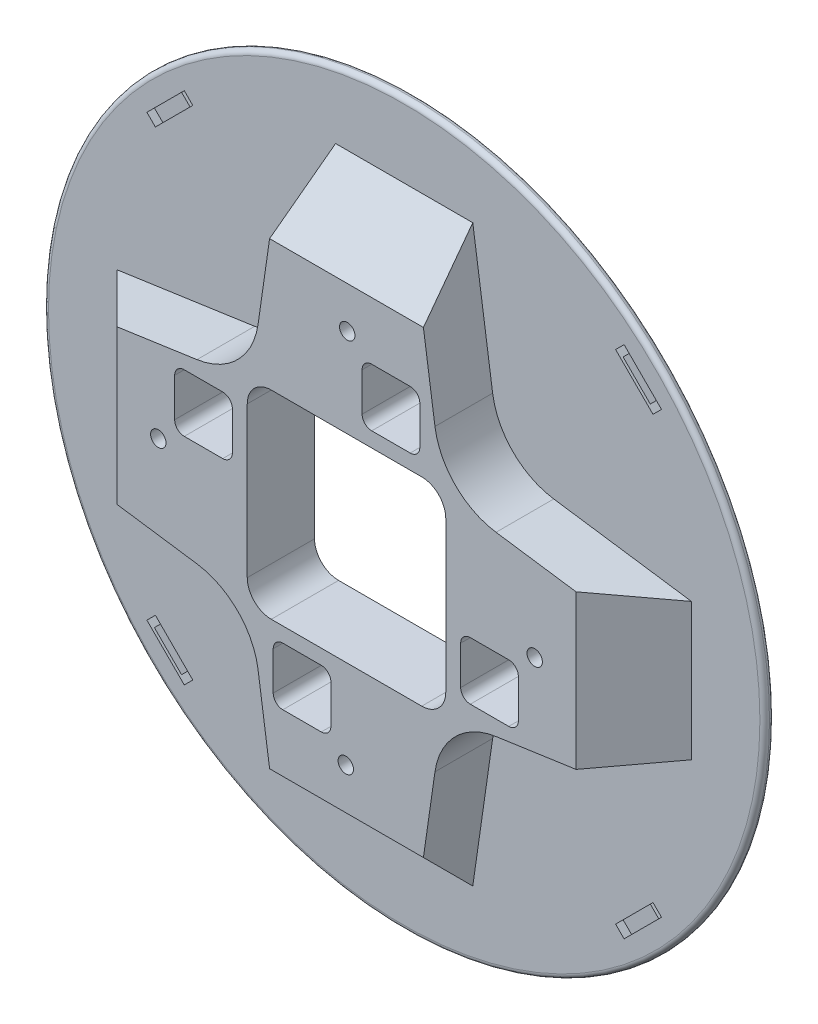
SolidWorks part; units mm, degrees
ref_plane "Front" through (0, 0, 0) normal (0, 0, 1) x (1, 0, 0)
ref_plane "Top" through (0, 0, 0) normal (0, 1, 0) x (1, 0, 0)
ref_plane "Right" through (0, 0, 0) normal (1, 0, 0) x (0, 0, -1)
sketch "ｽｹｯﾁ1" plane through (0, 0, 0) normal (0, 0, 1) x (1, 0, 0)
  line L1 (47.75, -47.75) -> (-47.75, -47.75)
  line L2 (47.75, -47.75) -> (47.75, 47.75)
  line L3 (47.75, 47.75) -> (-47.75, 47.75)
  line L4 (-47.75, -47.75) -> (-47.75, 47.75)
  line L5 (47.75, -47.75) -> (-47.75, 47.75) construction
  line L6 (47.75, 47.75) -> (-47.75, -47.75) construction
  point P0 (0, 0)
  dimension "D1" = 95.5
extrude "ﾎﾞｽ - 押し出し1" add sketch "ｽｹｯﾁ1" along normal blind 12
sketch "ｽｹｯﾁ2" plane through (0, 0, 12) normal (0, 0, 1) x (1, 0, 0)
  line L0 (-16, 47.75) -> (-20, 20)
  line L2 (-20, 20) -> (-47.75, 16)
  line L4 (-47.75, 16) -> (-47.75, 47.75)
  line L5 (-47.75, 47.75) -> (-16, 47.75)
  line L6 (-16, -47.75) -> (-20, -20)
  line L8 (-20, -20) -> (-47.75, -16)
  line L9 (-47.75, -16) -> (-47.75, -47.75)
  line L10 (-47.75, -47.75) -> (-16, -47.75)
  line L11 (0, 0) -> (-47.75, 47.75) construction
  line L12 (0, 0) -> (-47.75, -47.75) construction
  line L13 (-47.75, 47.75) -> (-47.75, -47.75) construction
  line L14 (-47.75, -47.75) -> (47.75, -47.75) construction
  dimension "D1" = 16
  dimension "D2" = 16
  dimension "D3" = 16
  dimension "D4" = 4
  dimension "D5" = 4
extrude "ｶｯﾄ - 押し出し1" cut sketch "ｽｹｯﾁ2" against normal through all
mirror "ﾐﾗｰ1" about plane through (0, 0, 0) normal (1, 0, 0) of "ｶｯﾄ - 押し出し1"
fillet "ﾌｨﾚｯﾄ2" radius 15 4 edges at (-20, 20, 6) (20, 20, 6) (20, -20, 6) (-20, -20, 6)
sketch "ｽｹｯﾁ3" plane through (0, 0, 0) normal (0, 0, -1) x (-1, 0, 0)
  circle A0 centre (0, 0) radius 75
  dimension "D1" = 150
extrude "ﾎﾞｽ - 押し出し2" add sketch "ｽｹｯﾁ3" along normal blind 2
chamfer "面取り1" distance 12 angle 45 4 edges at (0, 47.75, 0) (47.75, 0, 0) (0, -47.75, 0) (-47.75, 0, 0)
fillet "ﾌｨﾚｯﾄ1" radius 1 2 edges at (-75, 0, 0) (-75, 0, -2)
sketch "ｽｹｯﾁ5" plane through (0, 0, 0) normal (0, 0, 1) x (1, 0, 0)
  circle A0 centre (-34.25, 34.25) radius 1.6
  circle A1 centre (34.25, 34.25) radius 1.6
  circle A2 centre (34.25, -34.25) radius 1.6
  circle A3 centre (-34.25, -34.25) radius 1.6
  dimension "D1" = 3.2
extrude "ｶｯﾄ - 押し出し2" [suppressed] cut sketch "ｽｹｯﾁ5" against normal through all
sketch "ｽｹｯﾁ6" plane through (0, 0, 12) normal (0, 0, 1) x (1, 0, 0)
  line L1 (21, -21) -> (-21, -21)
  line L2 (21, -21) -> (21, 21)
  line L3 (21, 21) -> (-21, 21)
  line L4 (-21, -21) -> (-21, 21)
  line L5 (21, -21) -> (-21, 21) construction
  line L6 (21, 21) -> (-21, -21) construction
  point P0 (0, 0)
  dimension "D1" = 42
extrude "ｶｯﾄ - 押し出し3" cut sketch "ｽｹｯﾁ6" against normal through all
sketch "ｽｹｯﾁ7" plane through (0, 0, 12) normal (0, 0, 1) x (1, 0, 0)
  circle A0 centre (0.15, 39.15) radius 1.6
  circle A1 centre (-39.15, 0.15) radius 1.6
  circle A2 centre (39.15, -0.15) radius 1.6
  circle A3 centre (-0.15, -39.15) radius 1.6
  dimension "D5" = 3.2
extrude "ｶｯﾄ - 押し出し4" cut sketch "ｽｹｯﾁ7" against normal through all
chamfer "面取り2" [suppressed] distance 1.5 angle 45
sketch "ｽｹｯﾁ8" plane through (0, 0, -2) normal (0, 0, -1) x (-1, 0, 0)
  line L0 (-45.7487, 53.5269) -> (-46.8094, 52.4663)
  line L1 (-53.5269, 45.7487) -> (-51.7591, 43.981)
  line L2 (-51.7591, 43.981) -> (-50.6985, 45.0416)
  line L3 (-43.981, 51.7591) -> (-45.7487, 53.5269)
  line L4 (-52.4663, 46.8094) -> (-50.6985, 45.0416)
  line L5 (-45.0416, 50.6985) -> (-43.981, 51.7591)
  line L6 (-46.8094, 52.4663) -> (-45.0416, 50.6985)
  line L7 (-52.4663, 46.8094) -> (-53.5269, 45.7487)
  line L8 (53.033, -53.033) -> (-53.033, 53.033) construction
  line L9 (-21, 21) -> (21, 21) construction
  line L10 (-53.033, -53.033) -> (53.033, 53.033) construction
  line L11 (43.981, 51.7591) -> (45.0416, 50.6985)
  line L12 (51.7591, 43.981) -> (53.5269, 45.7487)
  line L13 (53.5269, 45.7487) -> (52.4663, 46.8094)
  line L14 (45.7487, 53.5269) -> (43.981, 51.7591)
  line L15 (46.8094, 52.4663) -> (45.0416, 50.6985)
  line L16 (46.8094, 52.4663) -> (45.7487, 53.5269)
  line L17 (52.4663, 46.8094) -> (50.6985, 45.0416)
  line L18 (50.6985, 45.0416) -> (51.7591, 43.981)
  circle A0 centre (0, 0) radius 75 construction
  point P14 (0, 0)
  point P21 (0, 0)
  dimension "D1" = 45
  dimension "D2" = 4
  dimension "D3" = 8
  dimension "D4" = 1.5
  dimension "D5" = 2.5
  dimension "D6" = 38
  dimension "D7" = 45
  dimension "D8" = 8
  dimension "D9" = 4
  dimension "D10" = 1.5
  dimension "D11" = 2.5
  dimension "D12" = 38
extrude "ｶｯﾄ - 押し出し5" cut sketch "ｽｹｯﾁ8" against normal through all
sketch "ｽｹｯﾁ9" plane through (0, 0, 0) normal (0, 0, 1) x (1, 0, 0)
  line L0 (-53.5269, 45.7487) -> (-45.7487, 53.5269)
  line L1 (-45.7487, 53.5269) -> (-43.981, 51.7591)
  line L2 (-43.981, 51.7591) -> (-51.7591, 43.981)
  line L3 (-51.7591, 43.981) -> (-53.5269, 45.7487)
  line L4 (43.981, 51.7591) -> (51.7591, 43.981)
  line L5 (51.7591, 43.981) -> (53.5269, 45.7487)
  line L6 (53.5269, 45.7487) -> (45.7487, 53.5269)
  line L7 (45.7487, 53.5269) -> (43.981, 51.7591)
extrude "ｶｯﾄ - 押し出し6" cut sketch "ｽｹｯﾁ9" against normal blind 0.5
mirror "ﾐﾗｰ2" about plane through (0, 0, 0) normal (0, 1, 0) of "ｶｯﾄ - 押し出し6", "ｶｯﾄ - 押し出し5"
sketch "ｽｹｯﾁ10" plane through (0, 0, 12) normal (0, 0, 1) x (1, 0, 0)
  line L1 (-35.75, 15.25) -> (-23.75, 15.25)
  line L2 (-35.75, 15.25) -> (-35.75, 3.25)
  line L3 (-35.75, 3.25) -> (-23.75, 3.25)
  line L4 (-23.75, 15.25) -> (-23.75, 3.25)
  line L5 (-15.25, -35.75) -> (-3.25, -35.75)
  line L6 (-15.25, -35.75) -> (-15.25, -23.75)
  line L7 (-15.25, -23.75) -> (-3.25, -23.75)
  line L8 (-3.25, -35.75) -> (-3.25, -23.75)
  line L9 (35.75, -15.25) -> (23.75, -15.25)
  line L10 (35.75, -15.25) -> (35.75, -3.25)
  line L11 (35.75, -3.25) -> (23.75, -3.25)
  line L12 (23.75, -15.25) -> (23.75, -3.25)
  line L13 (15.25, 35.75) -> (3.25, 35.75)
  line L14 (15.25, 35.75) -> (15.25, 23.75)
  line L15 (15.25, 23.75) -> (3.25, 23.75)
  line L16 (3.25, 35.75) -> (3.25, 23.75)
  line L18 (3.25, 25.75) -> (3.25, 33.75) construction
  line L19 (5.25, 23.75) -> (-3.75, 23.75) construction
  line L21 (23.75, -5.25) -> (23.75, 3.75) construction
  line L22 (-25.75, 3.25) -> (-33.75, 3.25) construction
  line L23 (-5.25, -23.75) -> (3.75, -23.75) construction
  line L25 (-13.25, -23.75) -> (-5.25, -23.75) construction
  line L29 (33.75, -15.25) -> (25.75, -15.25) construction
  line L30 (25.75, -3.25) -> (33.75, -3.25) construction
  line L34 (-3.25, -25.75) -> (-3.25, -33.75) construction
  line L35 (-23.75, 5.25) -> (-23.75, -3.75) construction
  dimension "D1" = 12
  dimension "D2" = 12
  dimension "D3" = 12
extrude "ｶｯﾄ - 押し出し7" cut sketch "ｽｹｯﾁ10" against normal through all
sketch "ｽｹｯﾁ11" plane through (0, 0, -2) normal (0, 0, -1) x (-1, 0, 0)
  line L1 (21, 21) -> (-21, 21)
  line L2 (21, 21) -> (21, -21)
  line L3 (21, -21) -> (-21, -21)
  line L4 (-21, 21) -> (-21, -21)
extrude "ﾎﾞｽ - 押し出し3" add sketch "ｽｹｯﾁ11" against normal through all
fillet "ﾌｨﾚｯﾄ3" radius 2 16 edges at (23.75, -3.25, 5) (23.75, -15.25, 5) (35.75, -15.25, 5) (35.75, -3.25, 5) (-3.25, -23.75, 5) (-3.25, -35.75, 5) (-15.25, -35.75, 5) (-15.25, -23.75, 5) (-35.75, 15.25, 5) (-35.75, 3.25, 5) (-23.75, 3.25, 5) (-23.75, 15.25, 5) (15.25, 35.75, 5) (15.25, 23.75, 5) (3.25, 23.75, 5) (3.25, 35.75, 5)
sketch "ｽｹｯﾁ12" plane through (0, 0, 12) normal (0, 0, 1) x (1, 0, 0)
  line L1 (20.65, -20.65) -> (-20.65, -20.65)
  line L2 (20.65, -20.65) -> (20.65, 20.65)
  line L3 (20.65, 20.65) -> (-20.65, 20.65)
  line L4 (-20.65, -20.65) -> (-20.65, 20.65)
  line L5 (20.65, -20.65) -> (-20.65, 20.65) construction
  line L6 (20.65, 20.65) -> (-20.65, -20.65) construction
  point P0 (0, 0)
  dimension "D1" = 41.3
extrude "ｶｯﾄ - 押し出し8" cut sketch "ｽｹｯﾁ12" against normal through all
fillet "ﾌｨﾚｯﾄ4" radius 5 4 edges at (-20.65, -20.65, 5) (20.65, -20.65, 5) (20.65, 20.65, 5) (-20.65, 20.65, 5)
sketch "ｽｹｯﾁ13" plane through (0, 0, -2) normal (0, 0, -1) x (-1, 0, 0)
  circle A0 centre (-0.15, 39.15) radius 3.25
  circle A1 centre (39.15, 0.15) radius 3.25
  circle A2 centre (-39.15, -0.15) radius 3.25
  circle A3 centre (0.15, -39.15) radius 3.25
  dimension "D1" = 6.5
extrude "ｶｯﾄ - 押し出し9" cut sketch "ｽｹｯﾁ13" against normal blind 3
